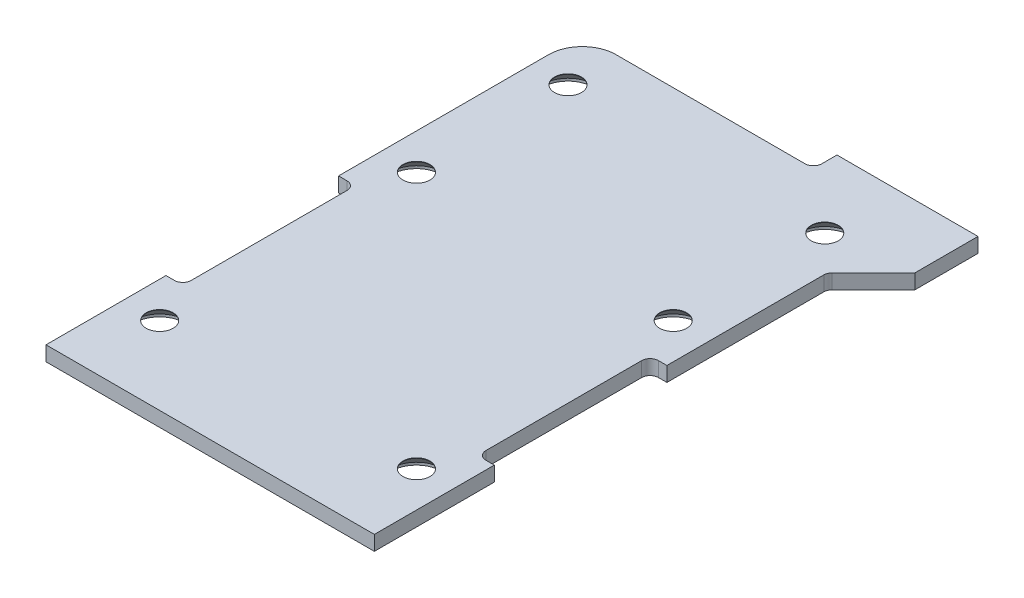
SolidWorks part; units mm, degrees
ref_plane "Front Plane" through (0, 0, 0) normal (0, 0, 1) x (1, 0, 0)
ref_plane "Top Plane" through (0, 0, 0) normal (0, 1, 0) x (1, 0, 0)
ref_plane "Right Plane" through (0, 0, 0) normal (1, 0, 0) x (0, 0, -1)
sketch "Sketch1" plane through (0, 0, 0) normal (0, 1, 0) x (1, 0, 0)
  line L1 (-18, 31.1) -> (18, 31.1)
  line L2 (-18, 31.1) -> (-18, -31.1)
  line L3 (-18, -31.1) -> (18, -31.1)
  line L4 (18, 31.1) -> (18, -31.1)
  line L5 (-18, 31.1) -> (18, -31.1) construction
  line L6 (-18, -31.1) -> (18, 31.1) construction
  point P0 (0, 0)
  dimension "D1" = 36
  dimension "D2" = 62.2
extrude "Base shape" add sketch "Sketch1" along normal blind 1.75
sketch "Sketch2" plane through (0, 1.75, 0) normal (0, 1, 0) x (1, 0, 0)
  line L0 (0, 31.1) -> (0, -31.1) construction
  line L1 (18, 31.1) -> (-18, 31.1) construction
  line L2 (-18, -31.1) -> (18, -31.1) construction
  line L4 (-18, 2.15) -> (-17.5, 2.15)
  line L5 (-18, 2.15) -> (-18, -18.35)
  line L6 (-18, -18.35) -> (-17.5, -18.35)
  line L7 (-17.5, 2.15) -> (-17.5, -18.35)
  line L8 (-17.5, -8.1) -> (-18, -8.1) construction
  line L9 (-15.25, -31.1) -> (-15.25, 31.1) construction
  line L11 (-18, -8.1) -> (18, -8.1) construction
  line L13 (15.25, 7.15) -> (15.25, -8.1) construction
  line L14 (15.25, 7.15) -> (0, 7.15) construction
  line L15 (18, -18.35) -> (17.5, -18.35)
  line L16 (17.5, 2.15) -> (17.5, -18.35)
  line L17 (18, 2.15) -> (17.5, 2.15)
  line L18 (18, 2.15) -> (18, -18.35)
  line L19 (18, -31.1) -> (18, 31.1) construction
  line L20 (-18, -31.1) -> (18, -31.1)
  line L21 (-18, -31.1) -> (-18, 14.9)
  line L22 (-18, 14.9) -> (18, 14.9)
  line L23 (18, -31.1) -> (18, 14.9)
  circle A0 centre (15.25, 7.15) radius 1.6
  circle A1 centre (15.25, -23.35) radius 1.6
  circle A2 centre (-15.25, 7.15) radius 1.6
  circle A3 centre (-15.25, -23.35) radius 1.6
  circle A4 centre (-15.25, 25.15) radius 1.6
  circle A5 centre (15.25, 25.15) radius 1.6
  line M13 (18, -31.1) -> (18, 31.1)
  line M15 (-18, 31.1) -> (-18, -31.1)
  dimension "D4" = 3.2
  dimension "D1" = 20.5
  dimension "D2" = 46
  dimension "D3" = 35
  dimension "D5" = 30.5
  dimension "D6" = 18
extrude "Cutouts" cut sketch "Sketch2" against normal up to next contours A2 | A0 | L17 L16 L15 M13 | L7 L4 L6 M15 | A3 | A1 | A4 | A5 region at (-17.75, 1.75, 8.1) region at (17.75, 1.75, 8.1) region at (15.25, 1.75, -7.15) region at (15.25, 1.75, 23.35) region at (-15.25, 1.75, -7.15) region at (-15.25, 1.75, 23.35)
sketch "Sketch3" plane through (0, 0, 0) normal (0, -1, 0) x (1, 0, 0)
  line L0 (18, -16.625) -> (19.5, -16.625) construction
  line L1 (19.5, 32.6) -> (-19.5, 32.6)
  line L2 (19.5, 32.6) -> (19.5, -32.6)
  line L3 (19.5, -32.6) -> (-19.5, -32.6)
  line L4 (-19.5, 32.6) -> (-19.5, -32.6)
  line L5 (19.5, 32.6) -> (-19.5, -32.6) construction
  line L6 (19.5, -32.6) -> (-19.5, 32.6) construction
  line L7 (0, -31.1) -> (0, -32.6) construction
  line L8 (-19.5, -31.1) -> (19.5, -31.1)
  line L9 (-19.5, -2.15) -> (19.5, -2.15)
  line L10 (-19.5, 18.35) -> (19.5, 18.35)
  line L11 (-19.5, 31.1) -> (19.5, 31.1)
  line L12 (-18, 18.35) -> (-17.5, 18.35)
  line L13 (-18, 31.1) -> (-18, 18.35)
  line L14 (18, 31.1) -> (-18, 31.1)
  line L15 (18, 18.35) -> (18, 31.1)
  line L16 (17.5, 18.35) -> (18, 18.35)
  line L17 (17.5, -2.15) -> (17.5, 18.35)
  line L18 (18, -2.15) -> (17.5, -2.15)
  line L19 (18, -31.1) -> (18, -2.15)
  line L20 (-18, -31.1) -> (18, -31.1)
  line L21 (-18, -2.15) -> (-18, -31.1)
  line L22 (-17.5, -2.15) -> (-18, -2.15)
  line L23 (-17.5, 18.35) -> (-17.5, -2.15)
  line L24 (-18, 18.35) -> (-17.5, 18.35)
  line L25 (-18, 31.1) -> (-18, 18.35)
  line L26 (18, 31.1) -> (-18, 31.1)
  line L27 (18, 18.35) -> (18, 31.1)
  line L28 (17.5, 18.35) -> (18, 18.35)
  line L29 (17.5, -2.15) -> (17.5, 18.35)
  line L30 (18, -2.15) -> (17.5, -2.15)
  line L31 (18, -31.1) -> (18, -2.15)
  line L32 (-18, -31.1) -> (18, -31.1)
  line L33 (-18, -2.15) -> (-18, -31.1)
  line L34 (-17.5, -2.15) -> (-18, -2.15)
  line L35 (-17.5, 18.35) -> (-17.5, -2.15)
  line L37 (24.7, -26.4) -> (24.7, -33.9) construction
  line L38 (7.95, -33.9) -> (24.7, -33.9) construction
  line L39 (7.95, -33.9) -> (7.95, -14.9) construction
  line L40 (24.7, -26.4) -> (19.5, -21.2) construction
  line L41 (24.7, -26.4) -> (24.7, -33.9)
  line L42 (7.95, -33.9) -> (24.7, -33.9)
  line L43 (7.95, -33.9) -> (7.95, -14.9)
  line L44 (24.7, -26.4) -> (19.5, -21.2)
  point P2 (0, 0)
  line M15 (18, -31.1) -> (18, -2.15)
  line M16 (18, 31.1) -> (-18, 31.1)
  line M17 (-18, 31.1) -> (-18, 18.35)
  line M35 (-18, -2.15) -> (-18, -31.1)
  line M36 (18, 18.35) -> (18, 31.1)
  dimension "D2" = 1.5
  dimension "D1" = 0
extrude "Extra size" add sketch "Sketch3" against normal up to surface (1.75 mm away) contours L9 L4 L8 M35 | L9 L8 L2 M15 | L11 L4 L10 M17 | L11 L10 L2 M36 | L4 L11 L2 L1 M16 | L43 L42 L41 L2 L3 | L43 L3 L2 L8 L32 region at (0, 0, 31.85) region at (18.75, 0, 24.725) region at (-18.75, 0, 24.725) region at (18.75, 0, -16.625) region at (-18.75, 0, -16.625) region at (20.0645, 0, -29.7415) region at (13.725, 0, -31.85) up to face at (15.25, 1.75, 24.95)
sketch "Sketch4" plane through (0, 0, 0) normal (0, 1, 0) x (1, 0, 0)
  circle A0 centre (-15.25, 25.15) radius 3
  circle A1 centre (15.25, 25.15) radius 3
  circle A2 centre (15.25, 7.15) radius 3
  circle A3 centre (-15.25, 7.15) radius 3
  circle A4 centre (-15.25, -23.35) radius 3
  circle A5 centre (15.25, -23.35) radius 3
  dimension "D1" = 6
extrude "Screw head cut" cut sketch "Sketch4" along normal blind 0.3
chamfer "Screw chamfer" distance 1.4 angle 45 6 edges at (-15.25, 0.3, 24.95) (15.25, 0.3, 24.95) (15.25, 0.3, -5.55) (15.25, 0.3, -23.55) (-15.25, 0.3, -23.55) (-15.25, 0.3, -5.55)
fillet "Front fillets" radius 4 1 edges at (-19.5, 0.875, -31.1)
fillet "Milling fillets" radius 1 6 edges at (17.5, 0.875, -2.15) (17.5, 0.875, 18.35) (-17.5, 0.875, -2.15) (-17.5, 0.875, 18.35) (19.5, 0.875, -21.2) (7.95, 0.875, -31.1)
